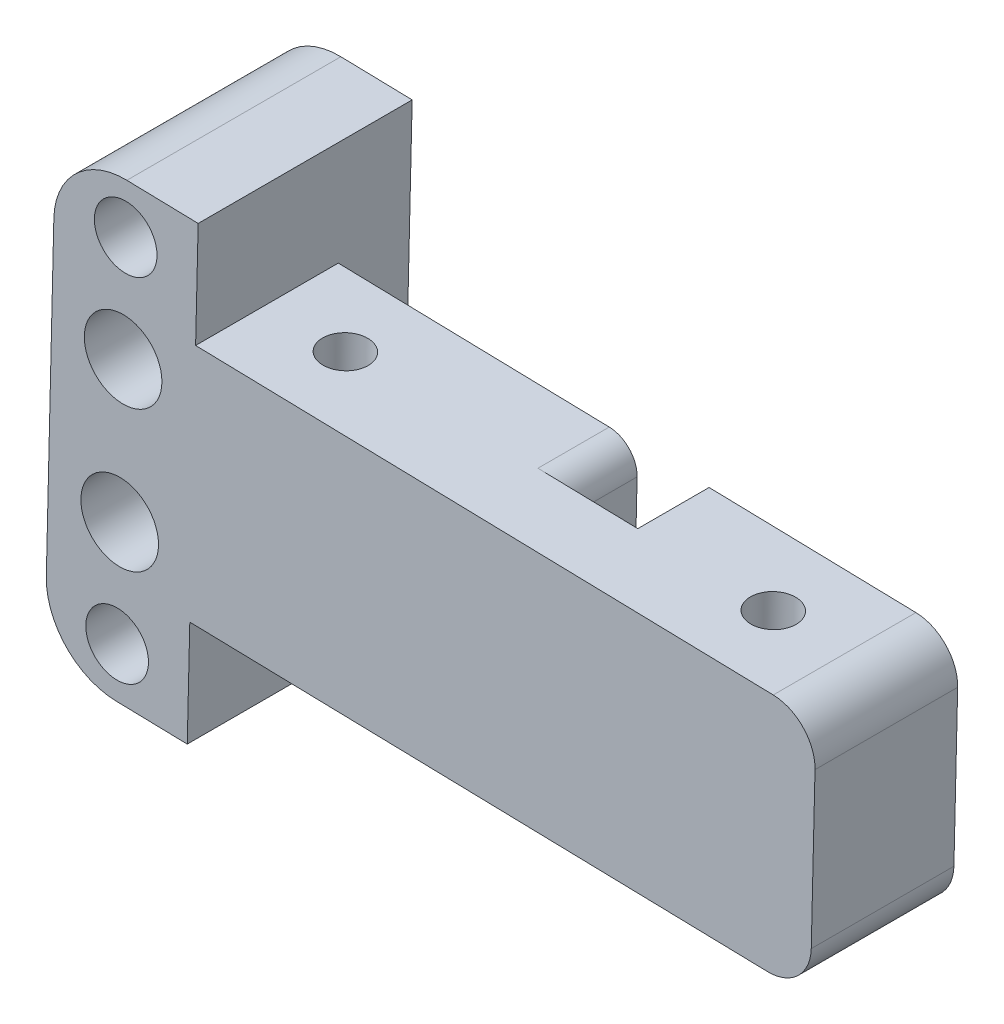
SolidWorks part; units mm, degrees
material "聚丁二烯(PB)"
ref_plane "前视基准面" through (0, 0, 0) normal (0, 0, 1) x (1, 0, 0)
ref_plane "上视基准面" through (0, 0, 0) normal (0, 1, 0) x (1, 0, 0)
ref_plane "右视基准面" through (0, 0, 0) normal (1, 0, 0) x (0, 0, -1)
other "Configuration Table"
sketch "草图1" plane through (0, 0, 0) normal (0, 0, 1) x (1, 0, 0)
  line L0 (24.1852, -7.0163) -> (24.4965, 5.98)
  line L1 (22.545, 8.0273) -> (-13.4447, 8.8895)
  line L2 (-13.4447, 8.8895) -> (-13.2651, 16.3873)
  line L3 (-13.2651, 16.3873) -> (-18.2636, 16.5071)
  line L4 (-23.3819, 11.6283) -> (-23.9088, -10.3654)
  line L5 (-19.03, -15.4837) -> (-14.0315, -15.6035)
  line L6 (-14.0315, -15.6035) -> (-13.8518, -8.1056)
  line L7 (-13.8518, -8.1056) -> (22.1378, -8.9678)
  arc A0 (24.4965, 5.98) -> (22.545, 8.0273) centre (22.4971, 6.0279) ccw
  arc A1 (-18.2636, 16.5071) -> (-23.3819, 11.6283) centre (-18.3834, 11.5085) ccw
  arc A2 (-23.9088, -10.3654) -> (-19.03, -15.4837) centre (-18.9103, -10.4852) ccw
  arc A3 (22.1378, -8.9678) -> (24.1852, -7.0163) centre (22.1857, -6.9684) ccw
  arc A4 (-16.7504, -12.0373) -> (-21.142, -11.9321) centre (-18.9462, -11.9847) ccw
  arc A5 (-21.142, -11.9321) -> (-16.7504, -12.0373) centre (-18.9462, -11.9847) ccw
  arc A6 (-16.0473, -4.552) -> (-21.4859, -4.4217) centre (-18.7666, -4.4869) ccw
  arc A7 (-21.4859, -4.4217) -> (-16.0473, -4.552) centre (-18.7666, -4.4869) ccw
  arc A8 (-15.8078, 5.4451) -> (-21.2464, 5.5754) centre (-18.5271, 5.5103) ccw
  arc A9 (-21.2464, 5.5754) -> (-15.8078, 5.4451) centre (-18.5271, 5.5103) ccw
  arc A10 (-16.1517, 12.9555) -> (-20.5432, 13.0607) centre (-18.3475, 13.0081) ccw
  arc A11 (-20.5432, 13.0607) -> (-16.1517, 12.9555) centre (-18.3475, 13.0081) ccw
extrude "凸台-拉伸1" add sketch "草图1" against normal blind 15
sketch "草图2" plane through (0, 0, -15) normal (0, 0, -1) x (-1, 0, 0)
  line L0 (13.4447, 8.8895) -> (13.8518, -8.1056)
  line L1 (13.8518, -8.1056) -> (-33.4158, -15.1213)
  line L2 (-33.4158, -15.1213) -> (-27.3795, 15.7432)
  line L3 (-27.3795, 15.7432) -> (13.4447, 8.8895)
extrude "切除-拉伸1" cut sketch "草图2" against normal blind 5
sketch "草图3" plane through (0.2051, 8.5625, 0) normal (0.024, 0.9997, 0) x (0.9997, -0.024, 0)
  line L0 (22.3463, 10) -> (-13.6537, 10) construction
  line L1 (12.3463, 10) -> (7.3463, 10)
  line L2 (12.3463, 10) -> (12.3463, 5)
  line L3 (12.3463, 5) -> (7.3463, 5)
  line L4 (7.3463, 10) -> (7.3463, 5)
  line L6 (24.3463, 10) -> (24.3463, 0) construction
  line L7 (22.3463, 0) -> (-13.6537, 0) construction
  circle A0 centre (21.8463, 5) radius 1.6
  circle A1 centre (-8.1537, 5) radius 1.6
  dimension "D3" = 2.5
  dimension "D4" = 3.2
  dimension "D1" = 5
  dimension "D2" = 12
  dimension "D6" = 5
  dimension "D5" = 2
extrude "切除-拉伸2" cut sketch "草图3" against normal blind 22
fillet "圆角1" radius 2 2 edges at (7.1421, -8.6086, -7.5) (7.5493, 8.3865, -7.5)
sketch "草图4" plane through (24.3393, -0.5831, 0) normal (0.9997, -0.024, 0) x (0, 0, -1)
  line L1 (0, 8.5649) -> (10, 8.5649)
  line L2 (0, 8.5649) -> (0, -8.4351)
  line L3 (0, -8.4351) -> (10, -8.4351)
  line L4 (10, 8.5649) -> (10, -8.4351)
extrude "凸台-拉伸2" add sketch "草图4" along normal blind 5.5 and the other way blind 3
sketch "草图5" plane through (0.2051, 8.5625, 0) normal (0.024, 0.9997, 0) x (0.9997, -0.024, 0)
  circle A0 centre (21.8463, 5) radius 1.6
extrude "切除-拉伸3" cut sketch "草图5" against normal blind 20.5
fillet "圆角2" radius 3 2 edges at (29.6357, -9.1475, -5) (30.0428, 7.8477, -5)
